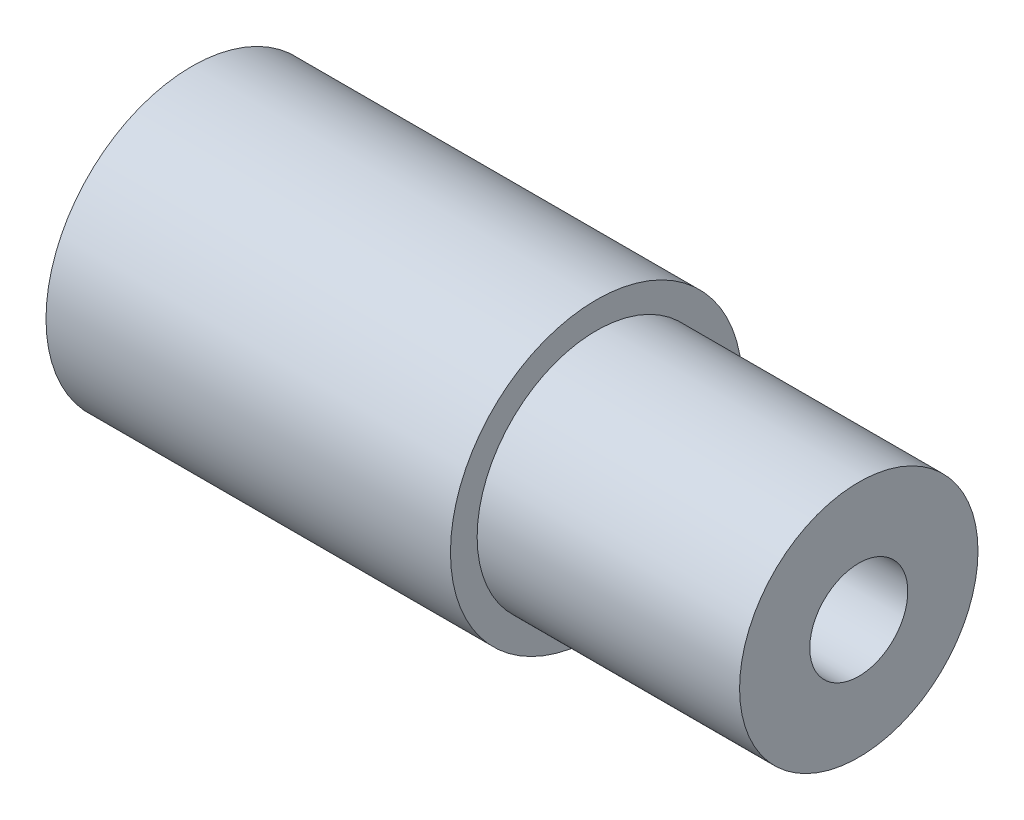
SolidWorks part; units mm, degrees
ref_plane "Front Plane" through (0, 0, 0) normal (0, 0, 1) x (1, 0, 0)
ref_plane "Top Plane" through (0, 0, 0) normal (0, 1, 0) x (1, 0, 0)
ref_plane "Right Plane" through (0, 0, 0) normal (1, 0, 0) x (0, 0, -1)
sketch "Reducer_T6_T4 Sketch" plane through (0, 0, 0) normal (0, 0, 1) x (1, 0, 0)
  line L0 (-1000, 0) -> (1000, 0) construction
  line L1 (-21.6, 0) -> (-21.6, 9.45)
  line L2 (-21.6, 9.45) -> (0.4, 9.45)
  line L3 (0.4, 9.45) -> (4.6, 9.45)
  line L4 (4.6, 9.45) -> (4.6, 7.722)
  line L5 (4.6, 7.722) -> (21.6, 7.722)
  line L6 (21.6, 7.722) -> (21.6, 0)
  line L7 (21.6, 0) -> (-21.6, 0)
revolve "Reducer_T6_T4" add sketch "Reducer_T6_T4 Sketch" angle 360 about L0
ref_axis "Engine Axis" through (23.76, 0, 0) along (-1, 0, 0)
sketch "Socket 1 Sketch" plane through (0, 0, 0) normal (0, 0, 1) x (1, 0, 0)
  line L0 (-1000, 0) -> (1000, 0) construction
  line L1 (-22.6, 0) -> (-22.6, 4.7625)
  line L2 (-22.6, 4.7625) -> (-4.8, 4.7625)
  line L3 (-4.8, 4.7625) -> (-4.8, 0)
  line L4 (-4.8, 0) -> (-22.6, 0)
revolve "Socket 1" cut sketch "Socket 1 Sketch" angle 360 about L0
sketch "Socket 2 Sketch" plane through (0, 0, 0) normal (0, 0, 1) x (1, 0, 0)
  line L0 (-1000, 0) -> (1000, 0) construction
  line L1 (6.4, 0) -> (6.4, 3.175)
  line L2 (6.4, 3.175) -> (22.6, 3.175)
  line L3 (22.6, 3.175) -> (22.6, 0)
  line L4 (22.6, 0) -> (6.4, 0)
revolve "Socket 2" cut sketch "Socket 2 Sketch" angle 360 about L0
